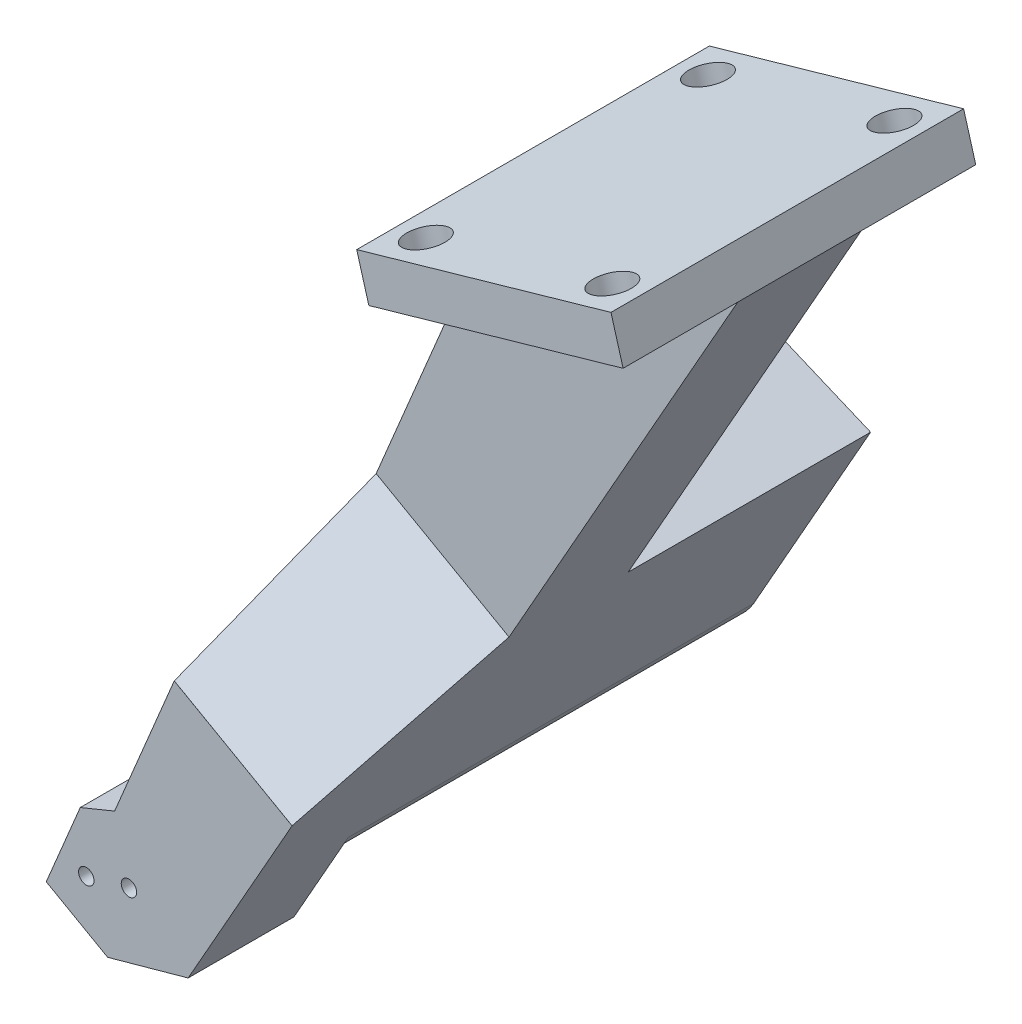
SolidWorks part; units mm, degrees
ref_plane "Front Plane" through (0, 0, 0) normal (0, 0, 1) x (1, 0, 0)
ref_plane "Top Plane" through (0, 0, 0) normal (0, 1, 0) x (1, 0, 0)
ref_plane "Right Plane" through (0, 0, 0) normal (1, 0, 0) x (0, 0, -1)
ref_plane "Plane1" through (0, 0, -8.2987) normal (0, 0, 1) x (1, 0, 0)
sketch "Sketch3" plane through (-20.6561, 72.1684, 0) normal (0.2752, -0.9614, 0) x (0.9614, 0.2752, 0)
  line L2 (96.7086, -28.2932) -> (66.7086, -28.2932)
  line L3 (96.7086, -28.2932) -> (96.7086, 11.7068)
  line L4 (96.7086, 11.7068) -> (66.7086, 11.7068)
  line L5 (66.7086, -28.2932) -> (66.7086, 11.7068)
  circle A0 centre (92.7086, 7.7068) radius 2.25
  circle A1 centre (70.7086, 7.7068) radius 2.25
  circle A2 centre (92.7086, -24.2932) radius 2.25
  circle A3 centre (70.7086, -24.2932) radius 2.25
  dimension "D8" = 4.5
  dimension "D1" = 30
  dimension "D2" = 40
  dimension "D3" = 20
  dimension "D4" = 4
  dimension "D5" = 4
  dimension "D6" = 4
  dimension "D7" = 4
  dimension "D9" = 5
extrude "Boss-Extrude1" add sketch "Sketch3" along normal blind 5
ref_plane "Plane2" through (0, 0, -8.2932) normal (0, 0, 1) x (1, 0, 0)
sketch "Sketch4" plane through (0, 0, -8.2932) normal (0, 0, 1) x (1, 0, 0)
  line L0 (73.6949, 93.9728) -> (44.8531, 85.7177)
  line L1 (44.8531, 85.7177) -> (21.8683, 30.7667)
  line L3 (34.0029, 23.7845) -> (73.6949, 93.9728)
  arc A0 (34.0029, 23.7845) -> (21.8683, 30.7667) centre (27.9356, 27.2756) cw
  dimension "D2" = 14
extrude "Boss-Extrude2" add sketch "Sketch4" along normal blind 7 and the other way blind 7
sketch "Sketch5" plane through (0, 0, -1.2932) normal (0, 0, 1) x (1, 0, 0)
  line L0 (34.0029, 23.7845) -> (39.6375, 33.7483)
  line L1 (34.0029, 23.7845) -> (73.6949, 93.9728) construction
  line L2 (39.6375, 33.7483) -> (26.2759, 41.3043)
  line L3 (44.8531, 85.7177) -> (21.8683, 30.7667) construction
  line L4 (26.2759, 41.3043) -> (21.8683, 30.7667)
  arc A0 (34.0029, 23.7845) -> (21.8683, 30.7667) centre (27.9356, 27.2756) cw
  arc A1 (21.8683, 30.7667) -> (34.0029, 23.7845) centre (27.9356, 27.2756) ccw construction
  dimension "D2" = 9.9638
extrude "Boss-Extrude3" add sketch "Sketch5" along normal up to surface (4.4932 mm away) contours L0 L2 L4 A0
sketch "Sketch6" plane through (0, 0, 3.2) normal (0, 0, 1) x (1, 0, 0)
  line L0 (14.3671, 12.8333) -> (22.1049, 16.0885)
  line L1 (20.85, 20.8766) -> (17.574, 20.5001)
  line L3 (17.574, 20.5001) -> (26.2759, 41.3043)
  line L4 (26.2759, 41.3043) -> (39.6375, 33.7483) construction
  line L5 (26.2759, 41.3043) -> (39.6375, 33.7483)
  line L6 (39.6375, 33.7483) -> (27.8513, 12.9066)
  line L7 (21.5157, 16.9419) -> (6.8507, 10.7725) construction
  line L8 (4.9493, 18.0275) -> (20.7552, 19.8439) construction
  line L10 (21.8683, 30.7667) -> (26.2759, 41.3043) construction
  line L11 (39.6375, 33.7483) -> (34.0029, 23.7845) construction
  line L12 (14.3671, 12.8333) -> (18.7194, 10.3721)
  line L13 (18.7194, 10.3721) -> (27.8513, 12.9066)
  arc A0 (22.1049, 16.0885) -> (20.85, 20.8766) centre (21.1355, 18.3929) ccw
  dimension "D1" = 5
  dimension "D2" = 45
  dimension "D3" = 5
extrude "Boss-Extrude4" add sketch "Sketch6" along normal up to surface (2 mm away) contours L1 L3 L5 L6 L13 L12 L0 A0
sketch "Sketch9" plane through (0, 0, 5.2) normal (0, 0, 1) x (1, 0, 0)
  line L0 (19.5123, 25.1343) -> (26.2759, 41.3043)
  line L1 (26.2759, 41.3043) -> (39.6375, 33.7483)
  line L2 (39.6375, 33.7483) -> (27.8513, 12.9066)
  line L3 (27.8513, 12.9066) -> (18.7194, 10.3721)
  line L4 (18.7194, 10.3721) -> (14.3671, 12.8333)
  line L5 (14.3671, 12.8333) -> (11.7558, 14.3101)
  line L6 (11.7558, 14.3101) -> (15.6146, 23.5356)
  line L7 (15.6146, 23.5356) -> (19.5123, 25.1343)
  dimension "D1" = 135
  dimension "D2" = 3
  dimension "D3" = 10
extrude "Boss-Extrude5" add sketch "Sketch9" along normal blind 10
sketch "Sketch8" plane through (0, 0, 3.2) normal (0, 0, 1) x (1, 0, 0)
  line L0 (21.1355, 18.3929) -> (16.2988, 17.1253) construction
  line L1 (20.85, 20.8766) -> (17.574, 20.5001) construction
  circle A0 centre (21.1355, 18.3929) radius 0.875
  circle A1 centre (16.2988, 17.1253) radius 0.875
  arc A3 (22.1049, 16.0885) -> (20.85, 20.8766) centre (21.1355, 18.3929) ccw construction
  dimension "D1" = 1.75
  dimension "D2" = 1.75
  dimension "D3" = 5
  dimension "D4" = 8.13
extrude "Cut-Extrude1" cut sketch "Sketch8" along normal through all
chamfer "Chamfer1" distance 16.49 angle 45 1 edges at (32.9567, 37.5263, -1.2932)
sketch "Sketch10" plane through (0, 0, 3.2) normal (0, 0, -1) x (-1, 0, 0)
  point P0 (-5.9, 14.4)
sketch "Sketch12" plane through (0, 0, -15.2932) normal (0, 0, -1) x (-1, 0, 0)
  line L0 (-21.4835, 29.9906) -> (-31.5235, 53.8501)
  line L1 (-44.8531, 85.7177) -> (-21.8683, 30.7667) construction
  line L2 (-31.5235, 53.8501) -> (-47.2604, 47.2281)
  line L3 (-34.0029, 23.7845) -> (-73.6949, 93.9728) construction
  line L4 (-47.2604, 47.2281) -> (-34.0029, 23.7845)
  arc A0 (-21.4835, 29.9906) -> (-34.0029, 23.7845) centre (-27.9356, 27.2756) cw
  arc A1 (-34.0029, 23.7845) -> (-21.8683, 30.7667) centre (-27.9356, 27.2756) ccw construction
  point P14 (-21.8683, 30.7667)
  dimension "D1" = 25.8858
extrude "Boss-Extrude6" add sketch "Sketch12" along normal offset from surface (27.5068 mm away) 10 up to face at (73.2363, 95.5752, -8.2932) offset beyond the face yes
ref_axis "Axis1" through (5.9, 14.4, 3.2) along (0, 0, -1)
sketch "Sketch13" plane through (0, 0, -42.8) normal (0, 0, -1) x (-1, 0, 0)
  line L0 (-0.8886, 21.5864) -> (-25.0316, 38.4224)
  line L1 (-21.4835, 29.9906) -> (-31.5235, 53.8501) construction
  line L2 (-25.0316, 38.4224) -> (-38.1011, 31.0315)
  line L3 (-47.2604, 47.2281) -> (-34.0029, 23.7845) construction
  line L4 (-38.1011, 31.0315) -> (-34.0029, 23.7845)
  line L5 (-10.8315, 7.1585) -> (-31.8757, 21.4898)
  line L6 (-34.0029, 23.7845) -> (-31.8757, 21.4898)
  circle A0 centre (-5.9, 14.4) radius 6.5431
  arc A1 (-10.8315, 7.1585) -> (-0.8886, 21.5864) centre (-5.9, 14.4) ccw
  arc A2 (-34.0029, 23.7845) -> (-21.1895, 29.144) centre (-27.9356, 27.2756) ccw construction
extrude "Boss-Extrude7" add sketch "Sketch13" against normal offset from surface (6 mm away) 1 offset beyond the face yes
